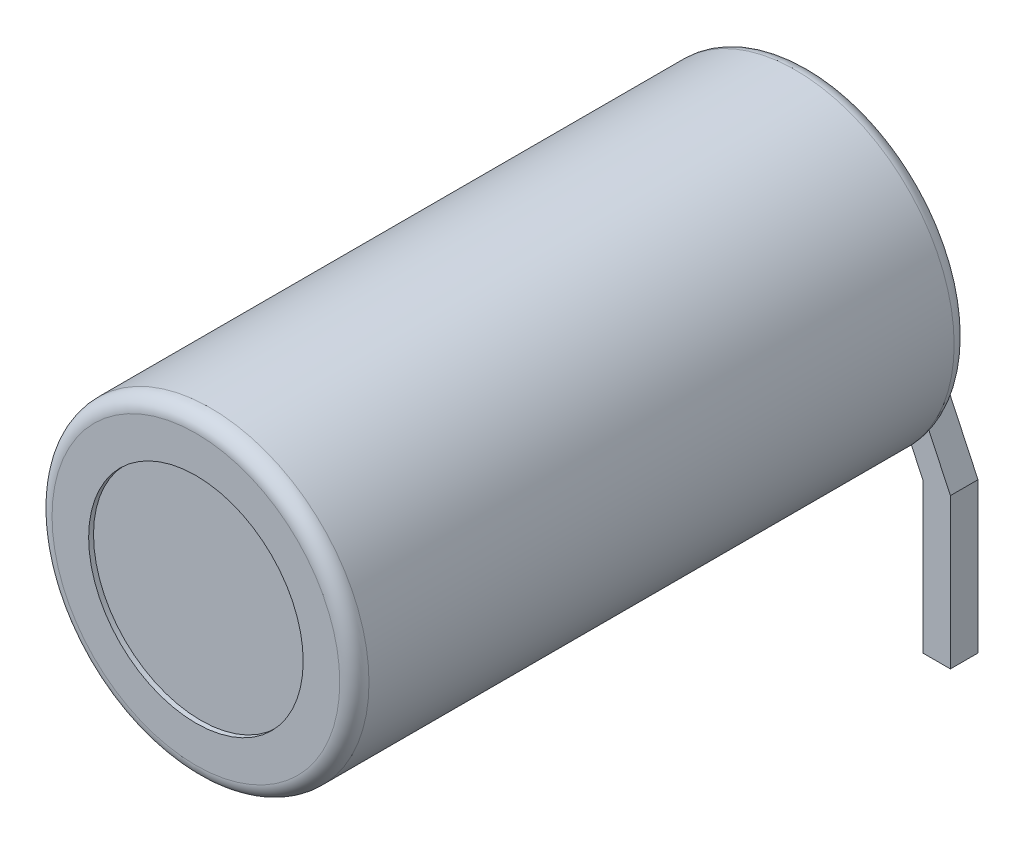
SolidWorks part; units mm, degrees
ref_plane "Front Plane" through (0, 0, 0) normal (0, 0, 1) x (1, 0, 0)
ref_plane "Top Plane" through (0, 0, 0) normal (0, 1, 0) x (1, 0, 0)
ref_plane "Right Plane" through (0, 0, 0) normal (1, 0, 0) x (0, 0, -1)
sketch "Sketch1" plane through (0, 0, 0) normal (1, 0, 0) x (0, 0, -1)
  line L0 (-6, 0.1) -> (6, 0.1)
  line L1 (-8.5106, 3.35) -> (8.5106, 3.35) construction
  line L2 (-6.3, 3.35) -> (-6.3, 0.4)
  line L3 (6.3, 3.35) -> (6.3, 0.4)
  line L4 (-6.2, 3.35) -> (-6.2, 0.4)
  line L5 (-6, 0.2) -> (6, 0.2)
  line L6 (6.2, 3.35) -> (6.2, 0.4)
  line L7 (-6.3, 3.35) -> (6.3, 3.35)
  line L8 (6.3, 1.15) -> (6.2, 1.15)
  line L9 (-6.3, 1.15) -> (-6.2, 1.15)
  arc A0 (-6, 0.1) -> (-6.3, 0.4) centre (-6, 0.4) cw
  arc A1 (6, 0.1) -> (6.3, 0.4) centre (6, 0.4) ccw
  arc A2 (-6, 0.2) -> (-6.2, 0.4) centre (-6, 0.4) cw
  arc A3 (6, 0.2) -> (6.2, 0.4) centre (6, 0.4) ccw
  point P4 (0, 3.35)
  point P5 (0, 0.1)
  dimension "D3" = 12.6
  dimension "D4" = 0.3
  dimension "D1" = 0.1
  dimension "D2" = 6.5
  dimension "D6" = 2.2
  dimension "D5" = 0.1
revolve "Revolve1" add sketch "Sketch1" angle 360 about L1 region at (0, 0.1968, 6.2032)
revolve "Revolve2" add sketch "Sketch1<4>" angle 360 about L1 region at (0, 1.7757, 0)
sketch "Sketch1<4>" plane through (0, 0, 0) normal (1, 0, 0) x (0, 0, -1) same geometry as "Sketch1"
sketch "Sketch2" plane through (0, 0, 0) normal (0, 0, 1) x (1, 0, 0)
  line L0 (0, 2.5) -> (-2.54, 2.5) construction
  line L1 (-2.54, 5) -> (2.54, 5) construction
  line L2 (-2.54, 5) -> (-2.54, 0) construction
  line L3 (-2.54, 0) -> (2.54, 0) construction
  line L4 (2.54, 5) -> (2.54, 0) construction
  line L5 (-2.54, 5) -> (2.54, 0) construction
  line L6 (-2.54, 0) -> (2.54, 5) construction
  line L7 (0, 2.5) -> (2.54, 2.5) construction
  line L8 (-2.54, 0) -> (-1.5, 2.5) construction
  line L9 (2.54, 0) -> (1.5, 2.5) construction
  line L10 (-2.2363, -3) -> (2.214, -3) construction
  point P0 (0, 2.5)
  point P13 (0, 0)
  point P14 (0, 0)
  point P15 (0, 0)
  dimension "D1" = 5
  dimension "D2" = 5.08
  dimension "D3" = 3
  dimension "D4" = 3
ref_plane "Plane4" through (0, 0, -6.35) normal (0, 0, -1) x (-1, 0, 0)
sketch "Sketch3" plane through (0, 0, -6.35) normal (0, 0, -1) x (-1, 0, 0)
  line L0 (-2.54, -3) -> (2.54, -3) construction
  line L1 (2.2363, -3) -> (-2.214, -3) construction
  line L2 (-2.823, -3) -> (-2.257, -3)
  line L3 (2.257, -3) -> (2.823, -3)
  line L4 (-2.257, -3) -> (-2.257, 0.2785)
  line L5 (2.54, 5) -> (-2.54, 0) construction
  line L6 (-2.257, 0.2785) -> (-1.217, 2.5)
  line L7 (0, 2.5) -> (-2.54, 2.5) construction
  line L8 (-1.217, 2.5) -> (-1.783, 2.5)
  line L9 (-2.823, -3) -> (-2.823, 0.2785)
  line L10 (-2.823, 0.2785) -> (-1.783, 2.5)
  line L11 (0, 0) -> (0, 5) construction
  line L12 (2.54, 5) -> (-2.54, 5) construction
  line L13 (1.217, 2.5) -> (1.783, 2.5)
  line L14 (2.257, 0.2785) -> (1.217, 2.5)
  line L15 (2.823, 0.2785) -> (1.783, 2.5)
  line L16 (2.823, -3) -> (2.823, 0.2785)
  line L17 (2.823, -3) -> (2.257, -3)
  line L18 (2.257, -3) -> (2.257, 0.2785)
  point P2 (0, -3)
  point P9 (-2.54, -3)
  point P12 (2.54, -3)
  point P21 (-1.5, 2.5)
  dimension "D1" = 5.08
  dimension "D2" = 0.566
  dimension "D3" = 0.566
extrude "Boss-Extrude1" add sketch "Sketch3" along normal blind 0.566 separate body contours L18 L3 L16 L15 L13 L14 | L10 L9 L2 L4 L6 L8 region at (2.33, -0.25, -6.35) region at (-2.33, -0.25, -6.35)
sketch "Sketch4" plane through (0, 0, -6.2) normal (0, 0, -1) x (-1, 0, 0)
  line L1 (-1.783, 3.066) -> (-1.217, 3.066)
  line L2 (-1.783, 3.066) -> (-1.783, 2.5)
  line L3 (-1.783, 2.5) -> (-1.217, 2.5)
  line L4 (-1.217, 3.066) -> (-1.217, 2.5)
  line L5 (-1.783, 3.066) -> (-1.217, 2.5) construction
  line L6 (-1.783, 2.5) -> (-1.217, 3.066) construction
  line L7 (1.217, 3.066) -> (1.783, 3.066)
  line L8 (1.217, 3.066) -> (1.217, 2.5)
  line L9 (1.217, 2.5) -> (1.783, 2.5)
  line L10 (1.783, 3.066) -> (1.783, 2.5)
  line L11 (1.217, 3.066) -> (1.783, 2.5) construction
  line L12 (1.217, 2.5) -> (1.783, 3.066) construction
  point P0 (-1.5, 2.783)
  point P5 (1.5, 2.783)
  point P10 (0, 0)
  point P11 (0, 0)
  point P12 (0, 0)
extrude "Boss-Extrude2" add sketch "Sketch4" along normal up to surface (0.716 mm away) up to face at (2.1933, -0.0738, -6.916)
sketch "Sketch5" plane through (0, -3, 0) normal (0, -1, 0) x (1, 0, 0)
  circle A0 centre (-2.54, -6.633) radius 0.4002 construction
chamfer "Chamfer1" distance 0.2 angle 45 8 edges at (-2.257, -3, -6.633) (-2.54, -3, -6.916) (-2.823, -3, -6.633) (-2.54, -3, -6.35) (2.823, -3, -6.633) (2.54, -3, -6.916) (2.257, -3, -6.633) (2.54, -3, -6.35)
